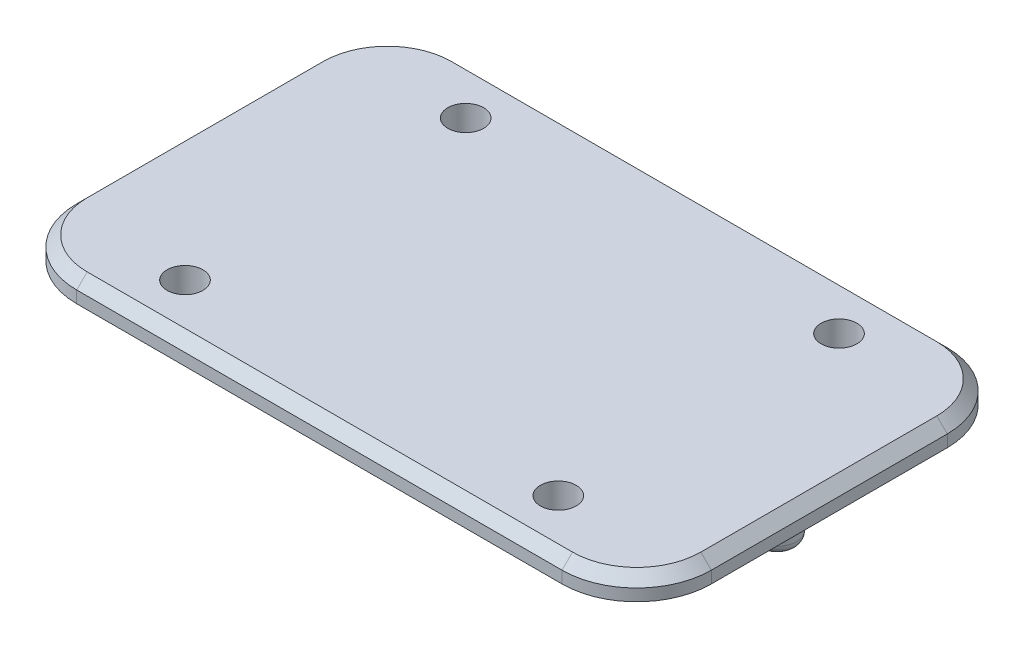
SolidWorks part; units mm, degrees
ref_plane "Front Plane" through (0, 0, 0) normal (0, 0, 1) x (1, 0, 0)
ref_plane "Top Plane" through (0, 0, 0) normal (0, 1, 0) x (1, 0, 0)
ref_plane "Right Plane" through (0, 0, 0) normal (1, 0, 0) x (0, 0, -1)
sketch "Sketch1" plane through (0, 0, 0) normal (0, 1, 0) x (1, 0, 0)
  line L0 (12.5, 10.7) -> (-12.5, 10.7)
  line L1 (-12.5, 8.1) -> (12.5, 8.1)
  line L4 (12.5, 10.9) -> (-12.5, 10.9) construction
  line L5 (-12.5, 7.9) -> (12.5, 7.9) construction
  line L8 (-12.5, -10.9) -> (12.5, -10.9) construction
  line L9 (12.5, -7.9) -> (-12.5, -7.9) construction
  line L12 (17.75, 1.5) -> (-17.75, 1.5) construction
  line L13 (-17.75, -1.5) -> (17.75, -1.5) construction
  line L14 (17.75, 1.3) -> (-17.75, 1.3)
  line L15 (-17.75, -1.3) -> (17.75, -1.3)
  line L16 (-12.5, -10.7) -> (12.5, -10.7)
  line L17 (12.5, -8.1) -> (-12.5, -8.1)
  line L18 (17.75, 0) -> (-17.75, 0) construction
  line L19 (-12.5, 9.4) -> (12.5, 9.4) construction
  line L20 (21.25, 12.9) -> (-21.25, 12.9)
  line L21 (21.25, 12.9) -> (21.25, -12.9)
  line L22 (21.25, -12.9) -> (-21.25, -12.9)
  line L23 (-21.25, 12.9) -> (-21.25, -12.9)
  line L24 (21.25, 12.9) -> (-21.25, -12.9) construction
  line L25 (21.25, -12.9) -> (-21.25, 12.9) construction
  line L26 (-12.5, -9.4) -> (12.5, -9.4) construction
  line L27 (0, 9.4) -> (0, -9.4) construction
  arc A0 (-12.5, 10.7) -> (-12.5, 8.1) centre (-12.5, 9.4) ccw
  arc A1 (12.5, 8.1) -> (12.5, 10.7) centre (12.5, 9.4) ccw
  arc A4 (-12.5, 10.9) -> (-12.5, 7.9) centre (-12.5, 9.4) ccw construction
  arc A5 (12.5, 7.9) -> (12.5, 10.9) centre (12.5, 9.4) ccw construction
  arc A8 (12.5, -10.9) -> (12.5, -7.9) centre (12.5, -9.4) ccw construction
  arc A9 (-12.5, -7.9) -> (-12.5, -10.9) centre (-12.5, -9.4) ccw construction
  arc A12 (17.75, -1.5) -> (17.75, 1.5) centre (17.75, 0) ccw construction
  arc A13 (-17.75, 1.5) -> (-17.75, -1.5) centre (-17.75, 0) ccw construction
  arc A14 (17.75, -1.3) -> (17.75, 1.3) centre (17.75, 0) ccw
  arc A15 (-17.75, 1.3) -> (-17.75, -1.3) centre (-17.75, 0) ccw
  arc A16 (12.5, -10.7) -> (12.5, -8.1) centre (12.5, -9.4) ccw
  arc A17 (-12.5, -8.1) -> (-12.5, -10.7) centre (-12.5, -9.4) ccw
  point P36 (0, 0)
  point P37 (0, 0)
  point P43 (-19.25, 0)
  point P59 (0, 0)
  dimension "D7" = 1.5
  dimension "D5" = 2
  dimension "D6" = 2
  dimension "D1" = 18.8
  dimension "D2" = 25
  dimension "D3" = 35.5
  dimension "D4" = 0.2
sketch "Sketch2" plane through (0, 0, 0) normal (0, 1, 0) x (1, 0, 0)
  line L0 (21.25, 12.9) -> (21.25, -12.9) construction
  line L1 (21.25, 12.9) -> (-21.25, 12.9) construction
  line L2 (-21.25, 12.9) -> (-21.25, -12.9) construction
  line L3 (21.25, -12.9) -> (-21.25, -12.9) construction
  line L4 (21.25, 12.9) -> (21.25, -12.9)
  line L5 (21.25, 12.9) -> (-21.25, 12.9)
  line L6 (-21.25, 12.9) -> (-21.25, -12.9)
  line L7 (21.25, -12.9) -> (-21.25, -12.9)
extrude "Boss-Extrude1" add sketch "Sketch2" along normal blind 1.5
fillet "Fillet1" radius 5 4 edges at (21.25, 0.75, 12.9) (21.25, 0.75, -12.9) (-21.25, 0.75, -12.9) (-21.25, 0.75, 12.9)
chamfer "Chamfer1" distance 0.7 angle 45 8 edges at (21.25, 1.5, 0) (19.7855, 1.5, -11.4355) (19.7855, 1.5, 11.4355) (0, 1.5, -12.9) (0, 1.5, 12.9) (-19.7855, 1.5, -11.4355) (-19.7855, 1.5, 11.4355) (-21.25, 1.5, 0)
sketch "Sketch3" plane through (0, 0, 0) normal (0, 1, 0) x (1, 0, 0)
  line L0 (-17.75, 0) -> (17.75, 0) construction
  line L1 (-12.5, -9.4) -> (12.5, -9.4) construction
  line L2 (-12.5, 9.4) -> (12.5, 9.4) construction
  line L3 (0, 9.4) -> (0, -9.4) construction
  line L4 (17.75, 1.3) -> (-17.75, 1.3)
  line L5 (-17.75, -1.3) -> (17.75, -1.3)
  line L8 (12.5, 10.7) -> (-12.5, 10.7)
  line L9 (-12.5, 8.1) -> (12.5, 8.1)
  line L16 (21.25, 12.9) -> (-21.25, 12.9) construction
  line L17 (-21.25, 12.9) -> (-21.25, -12.9) construction
  line L18 (-21.25, -12.9) -> (21.25, -12.9) construction
  line L19 (21.25, -12.9) -> (21.25, 12.9) construction
  line L20 (12.5, -8.1) -> (-12.5, -8.1)
  line L21 (-12.5, -10.7) -> (12.5, -10.7)
  arc A4 (-17.75, 1.3) -> (-17.75, -1.3) centre (-17.75, 0) ccw
  arc A5 (17.75, -1.3) -> (17.75, 1.3) centre (17.75, 0) ccw
  arc A8 (12.5, 8.1) -> (12.5, 10.7) centre (12.5, 9.4) ccw
  arc A9 (-12.5, 10.7) -> (-12.5, 8.1) centre (-12.5, 9.4) ccw
  arc A12 (-12.5, -8.1) -> (-12.5, -10.7) centre (-12.5, -9.4) ccw
  arc A13 (12.5, -10.7) -> (12.5, -8.1) centre (12.5, -9.4) ccw
  point P25 (0, 0)
  point P27 (0, 0)
  point P28 (0, 12.9)
  point P29 (-21.25, 0)
  point P30 (21.25, 0)
  point P31 (0, -12.9)
  dimension "D1" = 1.3
  dimension "D2" = 25
  dimension "D4" = 35.5
  dimension "D5" = 18.8
  dimension "D3" = 25.8
  dimension "D6" = 42.5
extrude "Boss-Extrude2" add sketch "Sketch3" against normal blind 1.5
ref_plane "Plane1" through (0, -3.5, 0) normal (0, 1, 0) x (1, 0, 0)
sketch "Sketch4" plane through (0, -1.5, 0) normal (0, -1, 0) x (1, 0, 0)
  line L2 (17.75, 1.3) -> (-17.75, 1.3)
  line L3 (-17.75, -1.3) -> (17.75, -1.3)
  line L4 (17.75, 1.3) -> (-17.75, 1.3)
  line L5 (-17.75, -1.3) -> (17.75, -1.3)
  arc A2 (17.75, -1.3) -> (17.75, 1.3) centre (17.75, 0) ccw
  arc A3 (-17.75, 1.3) -> (-17.75, -1.3) centre (-17.75, 0) ccw
  arc A4 (17.75, -1.3) -> (17.75, 1.3) centre (17.75, 0) ccw
  arc A5 (-17.75, 1.3) -> (-17.75, -1.3) centre (-17.75, 0) ccw
  dimension "D1" = 0
extrude "Boss-Extrude3" add sketch "Sketch4" along normal offset from surface (1.7 mm away) 0.3 up to plane "Plane1"
fillet "Fillet2" radius 0.6 4 edges at (-19.05, -3.2, 0) (0, -3.2, -1.3) (19.05, -3.2, 0) (0, -3.2, 1.3)
sketch "Sketch5" plane through (0, -1.5, 0) normal (0, -1, 0) x (1, 0, 0)
  line L0 (-12.5, 9.4) -> (12.5, 9.4) construction
  line L1 (-12.5, -9.4) -> (12.5, -9.4) construction
  line L6 (0, 9.4) -> (0, -9.4) construction
  circle A0 centre (-12.5, 9.4) radius 1.2
  circle A2 centre (12.5, -9.4) radius 1.5 construction
  circle A4 centre (12.5, 9.4) radius 1.5 construction
  circle A6 centre (-12.5, 9.4) radius 1.5 construction
  circle A8 centre (-12.5, -9.4) radius 1.5 construction
  circle A9 centre (12.5, 9.4) radius 1.2
  circle A14 centre (12.5, -9.4) radius 1.2
  circle A15 centre (-12.5, -9.4) radius 1.2
  point P3 (0, 0)
  dimension "D6" = 2.4
  dimension "D3" = 3
  dimension "D1" = 18.8
  dimension "D2" = 25
extrude "Cut-Extrude1" cut sketch "Sketch5" against normal through all
